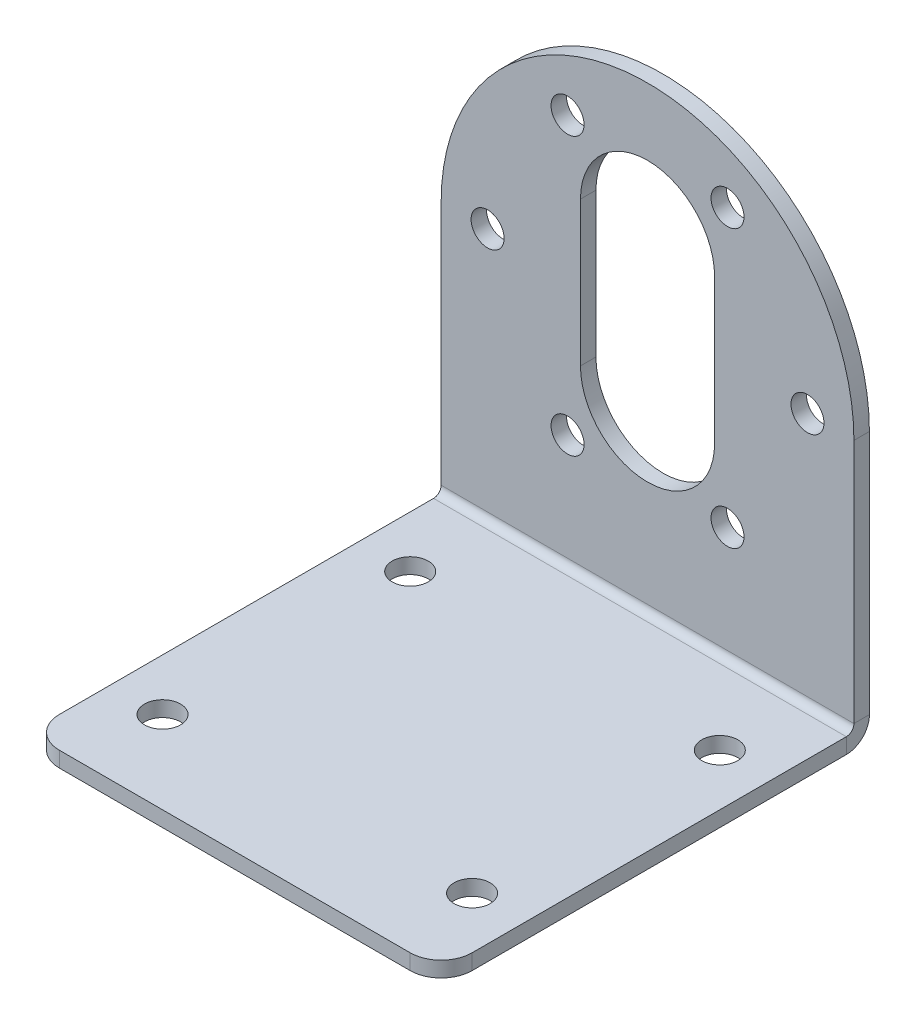
SolidWorks part; units mm, degrees
note: The reader was unsure of these and kept them because the rebuilt part matched: flange length of "边线-法兰1".
ref_plane "前视基准面" through (0, 0, 0) normal (0, 0, 1) x (1, 0, 0)
ref_plane "上视基准面" through (0, 0, 0) normal (0, 1, 0) x (1, 0, 0)
ref_plane "右视基准面" through (0, 0, 0) normal (1, 0, 0) x (0, 0, -1)
sketch "草图1" plane through (0, 0, 0) normal (0, 1, 0) x (1, 0, 0)
  line L1 (-17, -20) -> (17, -20)
  line L2 (-20, -17) -> (-20, 20)
  line L3 (-20, 20) -> (20, 20)
  line L4 (20, -17) -> (20, 20)
  line L5 (-20, -20) -> (20, 20) construction
  line L6 (-20, 20) -> (20, -20) construction
  arc A0 (-17, -20) -> (-20, -17) centre (-17, -17) cw
  arc A1 (17, -20) -> (20, -17) centre (17, -17) ccw
  point P0 (0, 0)
  dimension "D1" = 3
  dimension "D2" = 40
  dimension "D3" = 40
base flange "基体-法兰1" sketch "草图1" thickness 1.5 reverse thickness direction no parameters "D1"=0.7366
edge flange "边线-法兰1" sketch "草图8" flange angle 90 flange length 46 flange position material outside bend radius 0.7366 thickness 1.5 relief rectangular parameters "D6"=10
sketch "草图8" plane through (0, 0, -20) normal (0, 0, -1) x (-1, 0, 0)
  line L0 (-20, 0) -> (20, 0) construction
  line L1 (-20, 0) -> (20, 0)
  line L2 (-20, 0) -> (-20, 44.5)
  line L3 (-20, 44.5) -> (20, 44.5)
  line L4 (20, 44.5) -> (20, 0)
bend "边线折弯1" bend radius 0.7366 bend angle 90 parameters "D5"=1
sketch "草图9" plane through (0, 0, -21.5) normal (0, 0, -1) x (-1, 0, 0)
  line L0 (20, 0.7366) -> (20, 44.5) construction
  line L1 (-20, 44.5) -> (-20, 0.7366) construction
  line L2 (20, 44.5) -> (-20, 44.5) construction
  line L3 (-20, 24.5) -> (-20, 44.5)
  line L4 (-20, 44.5) -> (25.147, 48.5168)
  line L5 (25.147, 48.5168) -> (20, 24.5)
  arc A0 (20, 24.5) -> (-20, 24.5) centre (0, 24.5) ccw
extrude "切除-拉伸1" cut sketch "草图9" against normal blind 10 normal cut yes
sketch "草图10" plane through (0, 0, -21.5) normal (0, 0, -1) x (-1, 0, 0)
  line L0 (0, 24.5) -> (11.7459, 44.8446) construction
  line L1 (0, 24.5) -> (0, 51.1351) construction
  line L2 (-6.5, 17.5) -> (-6.5, 31.5)
  line L4 (6.5, 17.5) -> (6.5, 31.5)
  line L5 (-6.5, 17.5) -> (6.5, 31.5) construction
  line L6 (-6.5, 31.5) -> (6.5, 17.5) construction
  arc A0 (-6.5, 31.5) -> (6.5, 31.5) centre (0, 31.5) cw
  arc A1 (6.5, 17.5) -> (-6.5, 17.5) centre (0, 17.5) cw
  circle A2 centre (0, 24.5) radius 15.5 construction
  circle A3 centre (7.75, 37.9234) radius 1.6
  circle A4 centre (15.5, 24.5) radius 1.6
  circle A5 centre (7.75, 11.0766) radius 1.6
  circle A6 centre (-7.75, 11.0766) radius 1.6
  circle A7 centre (-15.5, 24.5) radius 1.6
  circle A8 centre (-7.75, 37.9234) radius 1.6
  point P0 (0, 24.5)
  point P27 (0, 24.5)
  dimension "D3" = 30
  dimension "D4" = 6
  dimension "D1" = 13
  dimension "D2" = 14
extrude "切除-拉伸2" cut sketch "草图10" against normal blind 10 normal cut yes
sketch "草图11" plane through (0, -1.5, 0) normal (0, -1, 0) x (1, 0, 0)
  line L0 (-17, 20) -> (17, 20) construction
  line L1 (20, 17) -> (20, -19.2634) construction
  circle A0 centre (15, 12) radius 1.75
  circle A1 centre (-15, 12) radius 1.75
  circle A2 centre (-15, -12) radius 1.75
  circle A3 centre (15, -12) radius 1.75
  dimension "D1" = 3.5
  dimension "D3" = 5
  dimension "D2" = 8
  dimension "D4" = 2
  dimension "D5" = 2
extrude "切除-拉伸3" cut sketch "草图11" against normal blind 10 normal cut yes
sketch "折弯-线1" plane through (0, 0, 0) normal (0, 1, 0) x (1, 0, 0)
sketch "边界框1" plane through (0, 0, 0) normal (0, 1, 0) x (1, 0, 0)
sheet metal parameters "钣金6" thickness 1.5 parameters "D1"=0.7366
flat pattern "平板型式6" [suppressed]
sketch "折弯-线2" plane through (0, 0, 0) normal (0, 1, 0) x (1, 0, 0)
sketch "边界框2" [suppressed] plane through (0, 0, 0) normal (0, 1, 0) x (1, 0, 0)
sheet metal parameters "钣金7" thickness 1.5 parameters "D1"=0.7366
flat pattern "平板型式6" [suppressed]
sketch "折弯-线2" plane through (0, 0, 0) normal (0, 1, 0) x (1, 0, 0)
sketch "边界框2" [suppressed] plane through (0, 0, 0) normal (0, 1, 0) x (1, 0, 0)
bend of the flat pattern "展开-<边线折弯1>1"
sheet metal parameters "钣金8" thickness 1.5 parameters "D1"=0.7366
flat pattern "平板型式6" [suppressed]
sketch "折弯-线2" plane through (0, 0, 0) normal (0, 1, 0) x (1, 0, 0)
sketch "边界框2" [suppressed] plane through (0, 0, 0) normal (0, 1, 0) x (1, 0, 0)
bend of the flat pattern "展开-<边线折弯1>1"
sheet metal parameters "钣金9" thickness 1.5 parameters "D1"=0.7366
flat pattern "平板型式6" [suppressed]
sketch "折弯-线2" plane through (0, 0, 0) normal (0, 1, 0) x (1, 0, 0)
sketch "边界框2" [suppressed] plane through (0, 0, 0) normal (0, 1, 0) x (1, 0, 0)
bend of the flat pattern "展开-<边线折弯1>1"
sheet metal parameters "钣金10" thickness 1.5 parameters "D1"=0.7366
flat pattern "平板型式6" [suppressed]
sketch "折弯-线2" plane through (0, 0, 0) normal (0, 1, 0) x (1, 0, 0)
sketch "边界框2" [suppressed] plane through (0, 0, 0) normal (0, 1, 0) x (1, 0, 0)
bend of the flat pattern "展开-<边线折弯1>1"
